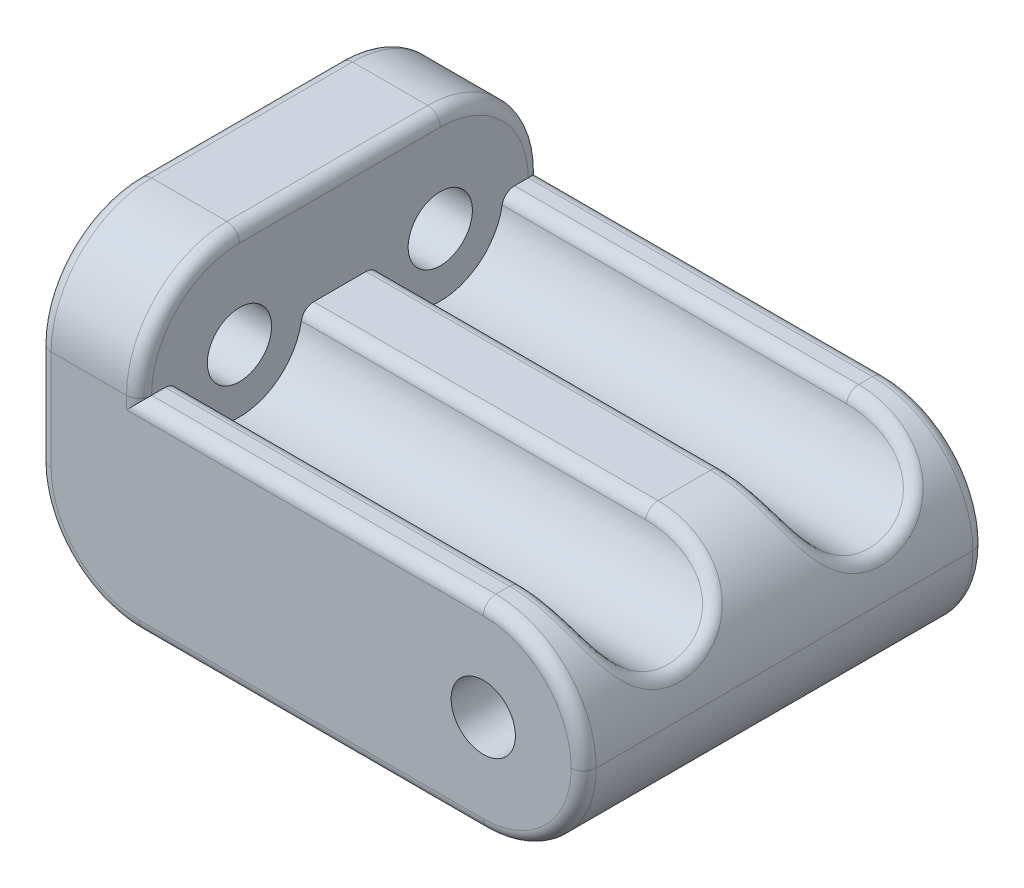
SolidWorks part; units mm, degrees
ref_plane "Front Plane" through (0, 0, 0) normal (0, 0, 1) x (1, 0, 0)
ref_plane "Top Plane" through (0, 0, 0) normal (0, 1, 0) x (1, 0, 0)
ref_plane "Right Plane" through (0, 0, 0) normal (1, 0, 0) x (0, 0, -1)
sketch "Sketch1" plane through (0, 0, 0) normal (1, 0, 0) x (0, 0, -1)
  line L0 (0, 0) -> (12.7, 0) construction
  line L1 (0, 6.35) -> (12.7, 6.35)
  line L2 (0, -6.35) -> (12.7, -6.35)
  arc A0 (0, 6.35) -> (0, -6.35) centre (0, 0) ccw
  arc A1 (12.7, -6.35) -> (12.7, 6.35) centre (12.7, 0) ccw
  circle A2 centre (12.7, 0) radius 2.032
  circle A3 centre (0, 0) radius 2.032
  point P3 (6.35, 0)
  dimension "D2" = 6.35
  dimension "D3" = 4.064
  dimension "D1" = 12.7
extrude "Boss-Extrude1" add sketch "Sketch1" along normal blind 6.35
sketch "Sketch4" plane through (0, 0, 0) normal (0, 0, 1) x (1, 0, 0)
  line L0 (0, 0) -> (0, -12.7)
  line L1 (0, -12.7) -> (34.4678, -12.7)
  line L2 (34.4678, -12.7) -> (34.4678, 0)
  line L3 (34.4678, 0) -> (0, 0)
  dimension "D1" = 34.4678
  dimension "D2" = 12.7
extrude "Boss-Extrude3" add sketch "Sketch4" along normal blind 6.35 and the other way blind 19.05
sketch "Sketch5" plane through (0, 0, 6.35) normal (0, 0, 1) x (1, 0, 0)
  line L0 (34.4678, -6.35) -> (28.1178, -6.35) construction
  line L1 (34.4678, -12.7) -> (34.4678, 0) construction
  line L2 (28.1178, -6.35) -> (28.1178, 0) construction
  line L3 (34.4678, 0) -> (6.35, 0) construction
  circle A0 centre (28.1178, -6.35) radius 2.032
  dimension "D1" = 4.064
extrude "Cut-Extrude1" cut sketch "Sketch5" against normal through all
sketch "Sketch6" plane through (34.4678, 0, 0) normal (1, 0, 0) x (0, 0, -1)
  circle A0 centre (0, 0) radius 2.032
  circle A1 centre (12.7, 0) radius 2.032
extrude "Cut-Extrude2" cut sketch "Sketch6" against normal through all both and the other way through all
sketch "Sketch7" plane through (34.4678, 0, 0) normal (1, 0, 0) x (0, 0, -1)
  circle A0 centre (0, 0) radius 3.9688
  circle A1 centre (12.7, 0) radius 3.9688
  dimension "D1" = 7.9375
fillet "Fillet1" radius 6.35 3 edges at (34.4678, -12.7, -6.35) (0, -12.7, -6.35)
extrude "Cut-Extrude3" cut sketch "Sketch7" against normal up to surface (28.1178 mm away) and the other way through all up to face at (6.35, 2.4243, -6.35)
fillet "Fillet2" radius 0.7937 6 edges at (34.0008, -3.9599, -12.4355) (34.0008, -3.9599, 0.2645) (17.2339, 0, -8.7312) (17.2339, 0, -16.6687) (17.2339, 0, 3.9688) (17.2339, 0, -3.9688)
fillet "Fillet3" radius 0.7937 18 edges at (0, -3.175, -19.05) (0, 4.4901, -17.1901) (0, 6.35, -6.35) (0, -3.175, 6.35) (17.2339, -12.7, -19.05) (32.6079, -10.8401, -19.05) (6.35, 4.4901, -17.1901) (6.35, 6.35, -6.35) (17.2339, -12.7, 6.35) (32.6079, -10.8401, 6.35) (0, 4.4901, 4.4901) (32.6079, -1.8599, -19.05) (6.35, 4.4901, 4.4901) (32.6079, -1.8599, 6.35) (17.2339, 0, -19.05) (17.2339, 0, 6.35) (1.8599, -10.8401, -19.05) (1.8599, -10.8401, 6.35)
